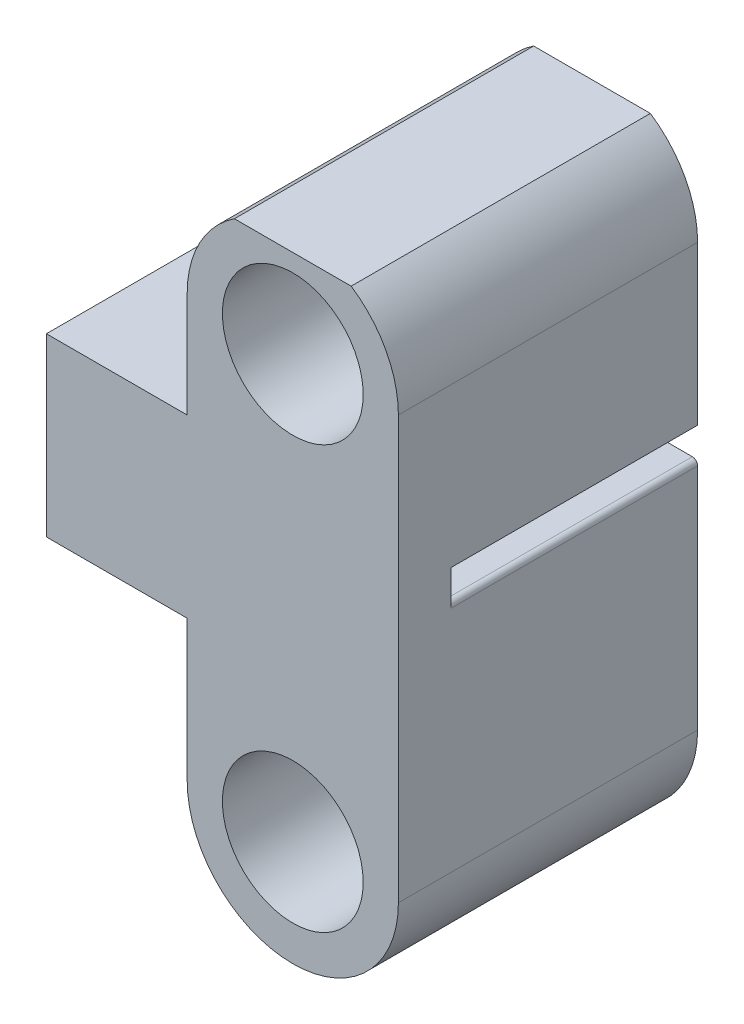
SolidWorks part; units mm, degrees
ref_plane "Front Plane" through (0, 0, 0) normal (0, 0, 1) x (1, 0, 0)
ref_plane "Top Plane" through (0, 0, 0) normal (0, 1, 0) x (1, 0, 0)
ref_plane "Right Plane" through (0, 0, 0) normal (1, 0, 0) x (0, 0, -1)
sketch "Sketch1" plane through (0, 0, 0) normal (0, 0, 1) x (1, 0, 0)
  line L0 (0, 0) -> (0, -12) construction
  line L1 (-3, 0) -> (-3, -12)
  line L2 (3, 0) -> (3, -12)
  arc A0 (3, 0) -> (-3, 0) centre (0, 0) ccw
  arc A1 (-3, -12) -> (3, -12) centre (0, -12) ccw
  circle A2 centre (0, 0) radius 2
  circle A3 centre (0, -12) radius 2
  dimension "D2" = 6
  dimension "D6" = 4
  dimension "D7" = 4
  dimension "D1" = 12
extrude "Boss-Extrude1" add sketch "Sketch1" along normal blind 8.5
sketch "Sketch2" plane through (3, 0, 0) normal (1, 0, 0) x (0, 0, -1)
  line L0 (-8.5, -6) -> (0, -6) construction
  line L1 (-8.5, -12) -> (-8.5, 0) construction
  line L2 (0, -12) -> (0, 0) construction
  line L3 (-4.25, 0) -> (-4.25, -12) construction
  line L4 (-8.5, 0) -> (0, 0) construction
  line L5 (-8.5, -12) -> (0, -12) construction
  circle A0 centre (-4.25, -8.5) radius 2
  dimension "D1" = 4
  dimension "D2" = 2.5
extrude "Cut-Extrude1" [suppressed] cut sketch "Sketch2" against normal through all
sketch "Sketch3" [suppressed] plane through (3, 0, 0) normal (1, 0, 0) x (0, 0, -1)
  line L1 (-0.6416, -8.5) -> (-2.4458, -5.375)
  line L2 (-2.4458, -5.375) -> (-6.0542, -5.375)
  line L3 (-6.0542, -5.375) -> (-7.8584, -8.5)
  line L4 (-7.8584, -8.5) -> (-6.0542, -11.625)
  line L5 (-6.0542, -11.625) -> (-2.4458, -11.625)
  line L6 (-2.4458, -11.625) -> (-0.6416, -8.5)
  line L7 (-1.8684, -4.375) -> (-6.6316, -4.375)
  line L8 (-6.6316, -4.375) -> (-9.0131, -8.5)
  line L9 (-9.0131, -8.5) -> (-6.6316, -12.625)
  line L10 (-6.6316, -12.625) -> (-1.8684, -12.625)
  line L11 (-1.8684, -12.625) -> (0.5131, -8.5)
  line L12 (0.5131, -8.5) -> (-1.8684, -4.375)
  circle A0 centre (-4.25, -8.5) radius 3.125 construction
  circle A1 centre (-4.25, -8.5) radius 4.125 construction
  dimension "D1" = 6.25
  dimension "D2" = 1
extrude "Boss-Extrude2" [suppressed] add sketch "Sketch3" along normal blind 2 and the other way blind 0.5
sketch "Sketch4" [suppressed] plane through (-3, 0, 0) normal (-1, 0, 0) x (0, 0, 1)
  line L0 (4.25, 0) -> (4.25, -6.5) construction
  line L1 (8.5, 0) -> (0, 0) construction
  line L3 (0.75, -2.75) -> (7.75, -2.75)
  line L4 (0.75, -2.75) -> (0.75, -5.75)
  line L5 (0.75, -5.75) -> (7.75, -5.75)
  line L6 (7.75, -2.75) -> (7.75, -5.75)
  line L7 (0.75, -2.75) -> (7.75, -5.75) construction
  line L8 (0.75, -5.75) -> (7.75, -2.75) construction
  circle A0 centre (4.25, -8.5) radius 2 construction
  point P7 (4.25, -4.25)
  dimension "D1" = 7
  dimension "D2" = 3
  dimension "D3" = 2.75
extrude "Cut-Extrude2" [suppressed] cut sketch "Sketch4" against normal through all
sketch "Sketch5" plane through (-3, 0, 0) normal (-1, 0, 0) x (0, 0, 1)
  line L0 (4.25, 0) -> (4.25, -12) construction
  line L1 (8.5, 0) -> (0, 0) construction
  line L2 (8.5, -12) -> (0, -12) construction
  line L3 (0, -6) -> (8.5, -6) construction
  line L4 (0, 0) -> (0, -12) construction
  line L5 (8.5, 0) -> (8.5, -12) construction
  line L7 (0, -15) -> (8.5, -15)
  line L8 (0, -15) -> (0, 3)
  line L9 (0, 3) -> (8.5, 3)
  line L10 (8.5, -15) -> (8.5, 3)
  line L11 (0, -15) -> (8.5, 3) construction
  line L12 (0, 3) -> (8.5, -15) construction
  point P12 (4.25, -6)
extrude "Cut-Extrude3" [suppressed] cut sketch "Sketch5" against normal through all flip side to cut
sketch "Sketch9" plane through (-3, 0, 0) normal (-1, 0, 0) x (0, 0, 1)
  line L0 (8.5, 0) -> (8.5, -12) construction
  line L1 (0, -3) -> (8.5, -3)
  line L2 (0, -3) -> (0, -8)
  line L3 (0, -8) -> (8.5, -8)
  line L4 (8.5, -3) -> (8.5, -8)
  line L5 (0, 0) -> (0, -12) construction
  line L6 (8.5, 0) -> (0, 0) construction
  dimension "D1" = 5
  dimension "D2" = 3
extrude "Boss-Extrude4" add sketch "Sketch9" along normal blind 4
sketch "Sketch6" plane through (3, 0, 0) normal (1, 0, 0) x (0, 0, -1)
  line L0 (0, -12) -> (0, 0) construction
  line L1 (0, -4.5) -> (-7, -4.5)
  line L2 (0, -4.5) -> (0, -6.1)
  line L3 (0, -6.1) -> (-7, -6.1)
  line L4 (-7, -4.5) -> (-7, -6.1)
  dimension "D1" = 1.6
  dimension "D2" = 4.5
  dimension "D3" = 7
extrude "Cut-Extrude5" cut sketch "Sketch6" against normal through all
sketch "Sketch7" plane through (0, 0, 7) normal (0, 0, -1) x (-1, 0, 0)
  line L0 (-3, -6.1) -> (-3, -5.5)
  line L1 (-3, -4.5) -> (-3, -6.1) construction
  line L2 (-2.85, -5.35) -> (-2.15, -5.35)
  line L3 (-2, -5.5) -> (-2, -6.1)
  line L4 (7, -6.1) -> (-3, -6.1) construction
  line L5 (-2, -6.1) -> (-3, -6.1)
  line L6 (-0.85, -5.35) -> (-0.15, -5.35)
  line L7 (0, -5.5) -> (0, -6.1)
  line L8 (0, -6.1) -> (-1, -6.1)
  line L9 (-1, -6.1) -> (-1, -5.5)
  line L10 (1.15, -5.35) -> (1.85, -5.35)
  line L11 (2, -5.5) -> (2, -6.1)
  line L12 (2, -6.1) -> (1, -6.1)
  line L13 (1, -6.1) -> (1, -5.5)
  line L14 (3.15, -5.35) -> (3.85, -5.35)
  line L15 (4, -5.5) -> (4, -6.1)
  line L16 (4, -6.1) -> (3, -6.1)
  line L17 (3, -6.1) -> (3, -5.5)
  line L18 (5.15, -5.35) -> (5.85, -5.35)
  line L19 (6, -5.5) -> (6, -6.1)
  line L20 (6, -6.1) -> (5, -6.1)
  line L21 (5, -6.1) -> (5, -5.5)
  arc A0 (-2.15, -5.35) -> (-2, -5.5) centre (-2.15, -5.5) cw
  arc A1 (-3, -5.5) -> (-2.85, -5.35) centre (-2.85, -5.5) cw
  arc A2 (-1, -5.5) -> (-0.85, -5.35) centre (-0.85, -5.5) cw
  arc A3 (-0.15, -5.35) -> (0, -5.5) centre (-0.15, -5.5) cw
  arc A4 (1, -5.5) -> (1.15, -5.35) centre (1.15, -5.5) cw
  arc A5 (1.85, -5.35) -> (2, -5.5) centre (1.85, -5.5) cw
  arc A6 (3, -5.5) -> (3.15, -5.35) centre (3.15, -5.5) cw
  arc A7 (3.85, -5.35) -> (4, -5.5) centre (3.85, -5.5) cw
  arc A8 (5, -5.5) -> (5.15, -5.35) centre (5.15, -5.5) cw
  arc A9 (5.85, -5.35) -> (6, -5.5) centre (5.85, -5.5) cw
  point P11 (-2, -5.35)
  point P14 (-3, -5.35)
  dimension "D3" = 0.15
  dimension "D1" = 1
  dimension "D2" = 0.75
  dimension "D4" = 5
extrude "Boss-Extrude3" add sketch "Sketch7" along normal through all
sketch "Sketch10" plane through (0, 0, 8.5) normal (0, 0, 1) x (1, 0, 0)
  line L1 (-2.5, 3.5) -> (2.5, 3.5)
  line L2 (-2.5, 3.5) -> (-2.5, 2.5)
  line L3 (-2.5, 2.5) -> (2.5, 2.5)
  line L4 (2.5, 3.5) -> (2.5, 2.5)
  line L5 (-2.5, 3.5) -> (2.5, 2.5) construction
  line L6 (-2.5, 2.5) -> (2.5, 3.5) construction
  arc A0 (3, 0) -> (-3, 0) centre (0, 0) ccw construction
  point P0 (0, 3)
  dimension "D1" = 1
  dimension "D2" = 5
extrude "Cut-Extrude6" cut sketch "Sketch10" against normal through all
equation "\"X-ROD-SPACING\"=45"
equation "\"Y-ROD-SPACING\"=75"
equation "\"Z-ROD-SPACING\"=17.5"
equation "\"Y-BED-OFFSET\"=2"
equation "\"Y-BED-ROD-INSET\"=3.5"
equation "\"Y-BED-SCREW-SPACING\"=209"
equation "\"Y-BED-SCREW-CUTOUT-SLOT-HEIGHT\"=2"
equation "\"T-SLOT-NUT-FILLET-RADIUS\"=0.5"
equation "\"T-SLOT-SCREW-SHAFT-RADIUS\"=1.55"
equation "\"T-SLOT-SCREW-SHAFT-CUTOUT-LENGTH\"=11"
equation "\"T-SLOT-NUT-DEPTH\"=3.5"
equation "\"T-SLOT-NUT-WIDTH\"=2.85"
equation "\"T-SLOT-NUT-END-DISTANCE\"=8"
equation "\"ACRYLIC-THICKNESS\"=10"
equation "\"ACRYLIC-THICKNESS2\"=4.5"
equation "\"ACRYLIC-TAB-CUTOUT-SIZE\"=\"ACRYLIC-THICKNESS\"+\"ACRYLIC-TAB-TOLERANCE\"*2"
equation "\"ACRYLIC-TAB-TOLERANCE\"=-.05"
equation "\"ACRYLIC-TAB-WIDTH\"=\"ACRYLIC-THICKNESS\""
equation "\"ACRYLIC-M3-HOLE\"=2.9"
equation "\"SMOOTHROD-CAP-SCREW-DISTANCE\"=20"
equation "\"FRAME-WIDTH-INNER\"=370"
equation "\"NEMA17-HOLE-SPACING\"=31"
equation "\"NEMA17-CENTRAL-CUTOUT\"=22.5"
equation "\"Z-BRACKET-REACH\"=55"
equation "\"Z-ROD-INSET\"=13.5"
equation "\"TOP-BRACKET-SPACING\"=40"
equation "\"SMOOTHROD-X-LENGTH\"=350"
equation "\"SMOOTHROD-Y-LENGTH\"=350"
equation "\"SMOOTHROD-Z-LENGTH\"=350"
equation "\"SMOOTHROD-TIGHTENING-HEADROOM\"=.25"
equation "\"LEADSCREW-Z-LENGTH\"=300"
equation "\"SCREW-LENGTH-FRAME\"=\"ACRYLIC-THICKNESS\" + 10"
equation "\"SCREW-LENGTH-MOTOR\"=\"ACRYLIC-THICKNESS\" + 5"
equation "\"SCREW-LENGTH-EXTRUDER\"=28"
equation "\"SCREW-HEAD-RADIUS\"=6"
equation "\"PRINTED-M3-HOLE\"=3.5"
equation "\"PRINTED-X-SMOOTHROD-DIAMETER\"=9.0"
equation "\"PRINTED-X-SMOOTHROD-CUTOUT\"=10"
equation "\"PRINTED-X-BASE-HEIGHT\"=10"
equation "\"PRINTED-LM8UU-CUTOUT-SIZE\"=15.5"
equation "\"PRINTED-LM8UU-CUTOUT-LENGTH\"=24.5"
equation "\"PRINTED-X-IDLER-HEIGHT\"=16"
equation "\"PRINTED-M3-NUT-AF\"=6.25"
equation "\"PSU-MOUNTING-WIDTH\"=95"
equation "\"PSU-MOUNTING-HEIGHT\"=177"
equation "\"Y-BELT-TO-ROD-DISTANCE\"=20"
equation "\"SPOOL-HOLDER-ROD-SPACING\"=150"
equation "\"ACRYLIC-X-CARRIAGE-WIDTH\"=55"
equation "\"ACRYLIC-X-CARRIAGE-HEIGHT\"=75"
equation "\"ACRYLIC-X-CARRIAGE-LM8UU-CUTOUT-WIDTH\"=24.25"
equation "\"ACRYLIC-X-CARRIAGE-LM8UU-CUTOUT-HEIGHT\"=11.0"
equation "\"ACRYLIC-X-CARRIAGE-SCREW-SPACING-X\"=15"
equation "\"ACRYLIC-X-CARRIAGE-SCREW-SPACING-Y\"=33"
equation "\"ACRYLIC-X-CARRIAGE-CENTER-TAB-SPACING\"=14"
equation "\"ACRYLIC-X-CARRIAGE-EXTRUDER-OFFSET\"=26"
equation "\"ACRYLIC-X-CARRIAGE-EXTRUDER-ANGLE\"=90"
equation "\"ACRYLIC-X-CARRIAGE-EXTRUDER-SHELF-DEPTH\"=\"ACRYLIC-X-CARRIAGE-EXTRUDER-OFFSET\" + 28"
equation "\"ACRYLIC-X-CARRIAGE-EXTRUDER-BRACE-SPACING\"=23"
equation "\"ACRYLIC-X-CARRIAGE-EXTRUDER-BRACE-TAB-OFFSET\"=20"
equation "\"ACRYLIC-X-CARRIAGE-EXTRUDER-BRACE-HEIGHT\"=35"
equation "\"ACRYLIC-X-CARRIAGE-EXTRUDER-BRACE-SCREW-SPACING\"=22"
equation "\"ACRYLIC-X-CARRIAGE-DUAL-WIDTH-MULTIPLIER\"=1.65"
equation "\"ACRYLIC-X-CARRIAGE-DUAL-HOTEND-SPACING\"=42"
equation "\"ACRYLIC-X-CARRIAGE-DUAL-WIDTH\"=75"
equation "\"ACRYLIC-X-CARRIAGE-DUAL-HOTEND-SEPARATION\"=36"
equation "\"ACRYLIC-X-CARRIAGE-DUAL-MOUNT-PLATE-DEPTH\"=75"
equation "\"ACRYLIC-X-CARRIAGE-DUAL-MOUNT-BRACE-WIDTH\"=33"
equation "\"ACRYLIC-X-CARRIAGE-DUAL-MOUNT-SCREW-WIDTH\"=40"
equation "\"BLOWER-FAN-WIDTH\"=15"
equation "\"D1@Sketch3\"=\"PRINTED-M3-NUT-AF\""
